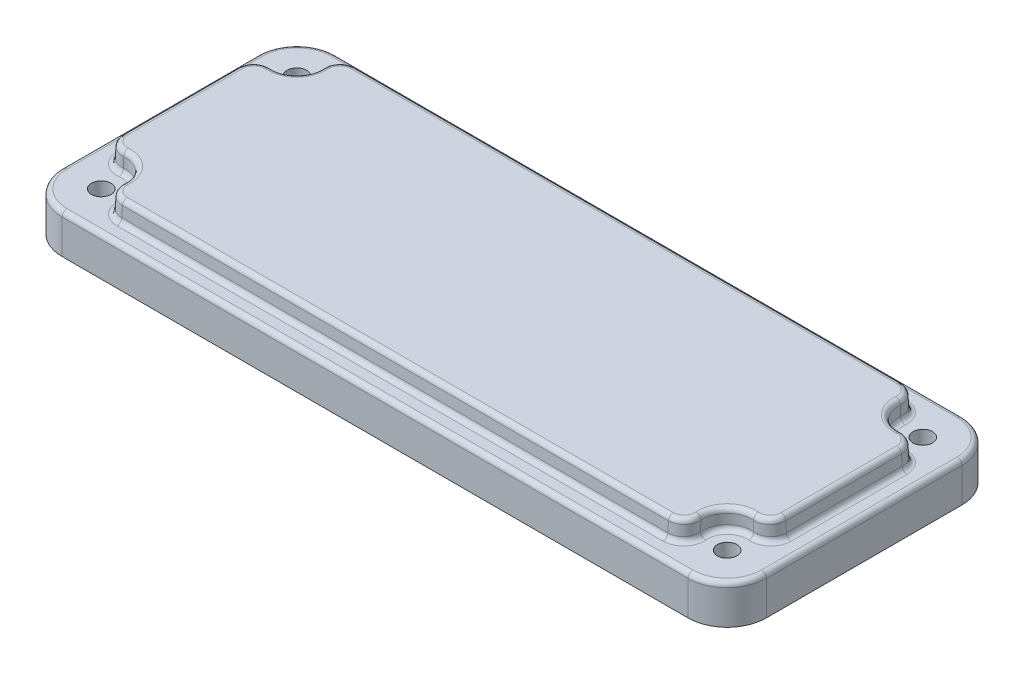
SolidWorks part; units mm, degrees
material "PW20:29:Sc:0:"
ref_plane "Front" through (0, 0, 0) normal (0, 0, 1) x (1, 0, 0)
ref_plane "Top" through (0, 0, 0) normal (0, 1, 0) x (1, 0, 0)
ref_plane "Right" through (0, 0, 0) normal (1, 0, 0) x (0, 0, -1)
sketch "Sketch1" plane through (0, 0, 0) normal (0, 1, 0) x (1, 0, 0)
  line L0 (-50.8, 22.225) -> (50.8, 22.225)
  line L1 (-57.15, 15.875) -> (-57.15, -15.875)
  line L2 (50.8, -22.225) -> (-50.8, -22.225)
  line L3 (57.15, -15.875) -> (57.15, 15.875)
  line L4 (-50.8, -15.875) -> (50.8, 15.875) construction
  arc A0 (-57.15, -15.875) -> (-50.8, -22.225) centre (-50.8, -15.875) ccw
  arc A1 (57.15, -15.875) -> (50.8, -22.225) centre (50.8, -15.875) cw
  arc A2 (50.8, 22.225) -> (57.15, 15.875) centre (50.8, 15.875) cw
  arc A3 (-50.8, 22.225) -> (-57.15, 15.875) centre (-50.8, 15.875) ccw
  dimension "D1" = 114.3
  dimension "D2" = 44.45
  dimension "D4" = 6.35
extrude "Base-Extrude" add sketch "Sketch1" along normal blind 6.35
sketch "Sketch2" plane through (0, 6.35, 0) normal (0, 1, 0) x (-1, 0, 0)
  line L4 (50.8, 19.05) -> (-50.8, 19.05)
  line L5 (-53.975, 15.875) -> (-53.975, -15.875)
  line L6 (-50.8, -19.05) -> (50.8, -19.05)
  line L7 (53.975, -15.875) -> (53.975, 15.875)
  line L8 (50.8, 19.05) -> (-50.8, 19.05)
  line L9 (-53.975, 15.875) -> (-53.975, -15.875)
  line L10 (-50.8, -19.05) -> (50.8, -19.05)
  line L11 (53.975, -15.875) -> (53.975, 15.875)
  arc A4 (53.975, 15.875) -> (50.8, 19.05) centre (50.8, 15.875) ccw
  arc A5 (53.975, 15.875) -> (50.8, 19.05) centre (50.8, 15.875) ccw
  arc A6 (-50.8, 19.05) -> (-53.975, 15.875) centre (-50.8, 15.875) ccw
  arc A7 (-50.8, 19.05) -> (-53.975, 15.875) centre (-50.8, 15.875) ccw
  arc A8 (-53.975, -15.875) -> (-50.8, -19.05) centre (-50.8, -15.875) ccw
  arc A9 (-53.975, -15.875) -> (-50.8, -19.05) centre (-50.8, -15.875) ccw
  arc A10 (50.8, -19.05) -> (53.975, -15.875) centre (50.8, -15.875) ccw
  arc A11 (50.8, -19.05) -> (53.975, -15.875) centre (50.8, -15.875) ccw
  dimension "D1" = 3.175
extrude "Boss-Extrude1" add sketch "Sketch2" along normal blind 3.175 draft 3
sketch "Sketch3" plane through (0, 9.525, 0) normal (0, 1, 0) x (-1, 0, 0)
  circle A0 centre (-50.8, 15.875) radius 3.9687
  dimension "D1" = 7.9375
extrude "Cut-Extrude1" cut sketch "Sketch3" against normal up to surface (3.175 mm away)
sketch "Sketch4" plane through (0, 6.35, 0) normal (0, 1, 0) x (-1, 0, 0)
  circle A0 centre (-50.8, 15.875) radius 1.5875
  dimension "D1" = 3.175
extrude "Cut-Extrude2" cut sketch "Sketch4" against normal through all
mirror "Mirror1" about plane through (0, 0, 0) normal (0, 0, 1) of "Cut-Extrude2", "Cut-Extrude1"
mirror "Mirror2" about plane through (0, 0, 0) normal (1, 0, 0) of "Mirror1"
fillet "Fillet1" radius 2.54 8 edges at (48.3138, 7.9044, 18.9685) (53.8935, 7.9044, 13.3888) (53.8935, 7.9044, -13.3888) (48.3138, 7.9044, -18.9685) (-48.3138, 7.9044, -18.9685) (-53.8935, 7.9044, -13.3888) (-53.8935, 7.9044, 13.3888) (-48.3138, 7.9044, 18.9685)
fillet "Fillet2" radius 0.7937 40 edges at (0, 6.35, -19.05) (0, 9.525, -18.8836) (-46.2625, 6.35, -18.1482) (46.1444, 6.35, -18.2787) (-45.8933, 9.525, -18.3276) (46.3986, 9.525, -17.785) (-47.9937, 6.35, -13.0687) (47.9937, 6.35, -13.0687) (-47.9937, 9.525, -13.0687) (47.9937, 9.525, -13.0687) (-53.2213, 6.35, -11.2022) (53.0648, 6.35, -11.3446) (-52.71, 9.525, -11.4736) (53.2526, 9.525, -10.9683) (0, 6.35, -22.225) (-53.975, 6.35, 0) (53.975, 6.35, 0) (-53.8086, 9.525, 0) (53.8086, 9.525, 0) (55.2901, 6.35, -20.3651) (-55.2901, 6.35, -20.3651) (-53.0383, 6.35, 11.3664) (53.2408, 6.35, 11.1827) (-53.2526, 9.525, 10.9683) (52.71, 9.525, 11.4736) (57.15, 6.35, 0) (-57.15, 6.35, 0) (-47.9937, 6.35, 13.0687) (47.9937, 6.35, 13.0687) (-47.9937, 9.525, 13.0687) (47.9937, 9.525, 13.0687) (55.2901, 6.35, 20.3651) (-55.2901, 6.35, 20.3651) (-46.1066, 6.35, 18.3169) (46.2919, 6.35, 18.1127) (-46.3986, 9.525, 17.785) (45.8933, 9.525, 18.3276) (0, 6.35, 22.225) (0, 6.35, 19.05) (0, 9.525, 18.8836)
sketch "Sketch5" plane through (0, 0, 0) normal (0, -1, 0) x (1, 0, 0)
  line L0 (-44.45, 15.875) -> (44.45, 15.875)
  line L1 (-44.45, 15.875) -> (-44.45, -15.875)
  line L2 (44.45, -15.875) -> (-44.45, -15.875)
  line L3 (44.45, -15.875) -> (44.45, 15.875)
  line L4 (50.8, 22.225) -> (-50.8, 22.225) construction
  line L5 (57.15, 15.875) -> (57.15, -15.875) construction
  line L6 (-57.15, -15.875) -> (-57.15, 15.875) construction
  line L7 (-50.8, -22.225) -> (50.8, -22.225) construction
  dimension "D1" = 6.35
  dimension "D2" = 12.7
  dimension "D3" = 12.7
  dimension "D4" = 6.35
extrude "Cut-Extrude3" cut sketch "Sketch5" against normal blind 6.35 draft 3
fillet "Fillet3" radius 6.35 4 edges at (44.2836, 3.175, 15.7086) (44.2836, 3.175, -15.7086) (-44.2836, 3.175, 15.7086) (-44.2836, 3.175, -15.7086)
fillet "Fillet4" radius 3.175 8 edges at (44.1172, 6.35, 0) (42.2609, 6.35, 13.6859) (42.2609, 6.35, -13.6859) (0, 6.35, 15.5422) (0, 6.35, -15.5422) (-42.2609, 6.35, 13.6859) (-42.2609, 6.35, -13.6859) (-44.1172, 6.35, 0)
